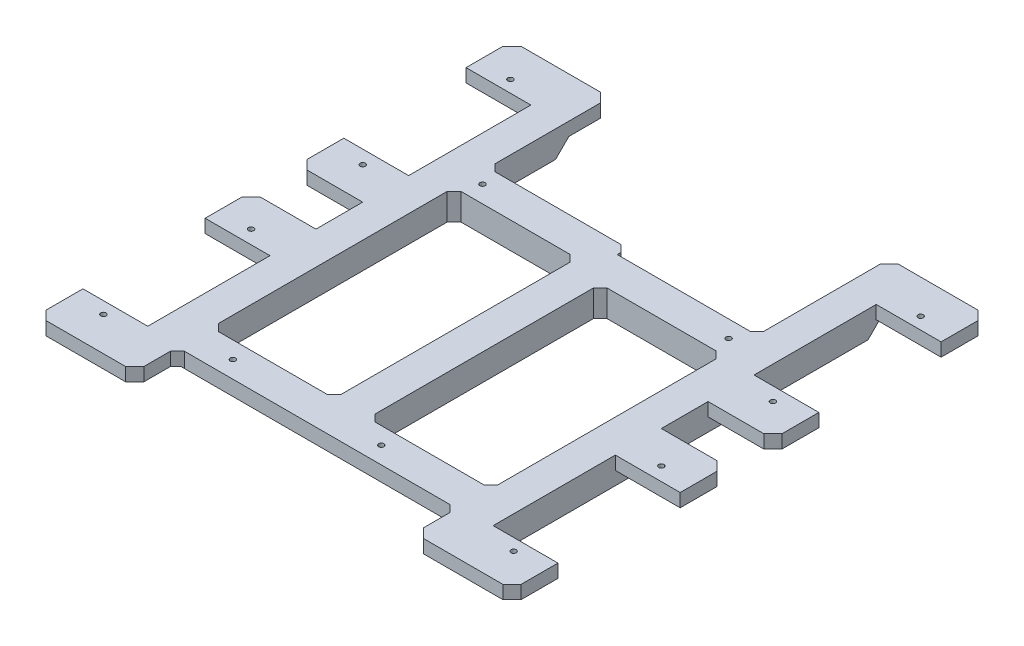
SolidWorks part; units mm, degrees
other "Markup1"
sketch "Sketch8" plane through (-44.7, 2.5, -44.7) normal (0, 1, 0) x (1, 0, 0)
sketch "Sketch10" plane through (-44.7, 2.5, -44.7) normal (0, 1, 0) x (1, 0, 0)
sketch "Sketch12" plane through (-44.7, 2.5, -44.7) normal (0, 1, 0) x (1, 0, 0)
sketch "Sketch14" plane through (-44.7, 2.5, -44.7) normal (0, 1, 0) x (1, 0, 0)
other "Markup2"
sketch "Sketch9" plane through (-44.7, 2.5, -44.7) normal (0, 1, 0) x (1, 0, 0)
sketch "Sketch11" plane through (-44.7, 2.5, -44.7) normal (0, 1, 0) x (1, 0, 0)
sketch "Sketch13" plane through (-44.7, 2.5, -44.7) normal (0, 1, 0) x (1, 0, 0)
sketch "Sketch15" plane through (-44.7, 2.5, -44.7) normal (0, 1, 0) x (1, 0, 0)
ref_plane "Front Plane" through (0, 0, 0) normal (0, 0, 1) x (1, 0, 0)
ref_plane "Top Plane" through (0, 0, 0) normal (0, 1, 0) x (1, 0, 0)
ref_plane "Right Plane" through (0, 0, 0) normal (1, 0, 0) x (0, 0, -1)
sketch "Sketch1" plane through (0, 0, 0) normal (0, 1, 0) x (1, 0, 0)
  line L0 (0, 44.7) -> (0, -44.7) construction
  line L1 (44.7, -44.7) -> (-44.7, -44.7)
  line L2 (44.7, -44.7) -> (44.7, 44.7)
  line L3 (44.7, 44.7) -> (-44.7, 44.7)
  line L4 (-44.7, -44.7) -> (-44.7, 44.7)
  line L5 (44.7, -44.7) -> (-44.7, 44.7) construction
  line L6 (44.7, 44.7) -> (-44.7, -44.7) construction
  circle A4 centre (-38.6, 38.3) radius 0.5
  circle A5 centre (-38.6, 10.5) radius 0.5
  circle A6 centre (-38.6, -10.5) radius 0.5
  circle A7 centre (-38.6, -38.3) radius 0.5
  circle A16 centre (38.6, -38.3) radius 0.5
  circle A17 centre (38.6, -10.5) radius 0.5
  circle A18 centre (38.6, 10.5) radius 0.5
  circle A19 centre (38.6, 38.3) radius 0.5
  point P0 (0, 0)
  point P6 (0, 0)
  dimension "D17" = 1
  dimension "D20" = 1
  dimension "D23" = 1
  dimension "D26" = 1
  dimension "D1" = 89.4
  dimension "D2" = 89.4
  dimension "D18" = 6.4
  dimension "D19" = 6.1
  dimension "D21" = 6.1
  dimension "D22" = 27.8
  dimension "D24" = 6.1
  dimension "D25" = 6.4
  dimension "D27" = 6.1
  dimension "D28" = 27.8
extrude "Boss-Extrude1" add sketch "Sketch1" along normal blind 2.5
sketch "Sketch5" plane through (0, 0, 0) normal (0, -1, 0) x (1, 0, 0)
  line L1 (32.5, -37) -> (-32.5, -37)
  line L2 (32.5, -37) -> (32.5, 37)
  line L3 (32.5, 37) -> (-32.5, 37)
  line L4 (-32.5, -37) -> (-32.5, 37)
  line L5 (32.5, -37) -> (-32.5, 37) construction
  line L6 (32.5, 37) -> (-32.5, -37) construction
  point P0 (0, 0)
  dimension "D1" = 65
  dimension "D2" = 74
extrude "Boss-Extrude3" add sketch "Sketch5" along normal blind 2.5
sketch "Sketch7" plane through (0, 2.5, 0) normal (0, 1, 0) x (1, 0, 0)
  line L1 (30.5, -35) -> (-30.5, -35) construction
  line L2 (30.5, -35) -> (30.5, 35) construction
  line L3 (30.5, 35) -> (-30.5, 35) construction
  line L4 (-30.5, -35) -> (-30.5, 35) construction
  line L5 (30.5, -35) -> (-30.5, 35) construction
  line L6 (30.5, 35) -> (-30.5, -35) construction
  circle A0 centre (-24.15, 18.595) radius 0.5
  circle A1 centre (24.15, 16.605) radius 0.5
  circle A2 centre (-19.07, -33.475) radius 0.5
  circle A3 centre (8.86, -33.475) radius 0.5
  point P0 (0, 0)
  dimension "D3" = 1
  dimension "D6" = 1
  dimension "D9" = 1
  dimension "D12" = 1
  dimension "D13" = 3.05
  dimension "D1" = 70
  dimension "D2" = 61
  dimension "D4" = 6.35
  dimension "D5" = 52.07
  dimension "D7" = 6.35
  dimension "D8" = 50.08
  dimension "D10" = 3.05
  dimension "D11" = 11.43
  dimension "D14" = 21.64
extrude "Cut-Extrude2" cut sketch "Sketch7" against normal blind 4
sketch "Sketch2" plane through (0, 2.5, 0) normal (0, 1, 0) x (1, 0, 0)
  line L0 (44.7, 44.7) -> (-44.7, 44.7) construction
  line L1 (-44.7, 40.6) -> (-32.5, 40.6) construction
  line L2 (-44.7, 40.6) -> (-44.7, 8.5) construction
  line L3 (-44.7, 8.5) -> (-32.5, 8.5) construction
  line L4 (-32.5, 40.6) -> (-32.5, 8.5) construction
  line L5 (-44.7, 40.6) -> (-32.5, 8.5) construction
  line L6 (-44.7, 8.5) -> (-32.5, 40.6) construction
  line L7 (-44.7, 44.7) -> (-44.7, -44.7) construction
  line L8 (0, 44.7) -> (0, -44.7) construction
  line L9 (-44.7, -44.7) -> (44.7, -44.7) construction
  line L10 (-44.7, 0) -> (44.7, 0) construction
  line L11 (44.7, -44.7) -> (44.7, 44.7) construction
  line L12 (-44.7, -8.5) -> (-32.5, -40.6) construction
  line L13 (-44.7, -40.6) -> (-32.5, -8.5) construction
  line L14 (-32.5, -40.6) -> (-32.5, -8.5) construction
  line L15 (-44.7, -8.5) -> (-32.5, -8.5) construction
  line L16 (-44.7, -40.6) -> (-44.7, -8.5) construction
  line L17 (-44.7, -40.6) -> (-32.5, -40.6) construction
  line L18 (44.7, -40.6) -> (32.5, -40.6) construction
  line L19 (44.7, -40.6) -> (44.7, -8.5) construction
  line L20 (44.7, -8.5) -> (32.5, -8.5) construction
  line L21 (32.5, -40.6) -> (32.5, -8.5) construction
  line L22 (44.7, -40.6) -> (32.5, -8.5) construction
  line L23 (44.7, -8.5) -> (32.5, -40.6) construction
  line L24 (44.7, 8.5) -> (32.5, 40.6) construction
  line L25 (44.7, 40.6) -> (32.5, 8.5) construction
  line L26 (32.5, 40.6) -> (32.5, 8.5) construction
  line L27 (44.7, 8.5) -> (32.5, 8.5) construction
  line L28 (44.7, 40.6) -> (44.7, 8.5) construction
  line L29 (44.7, 40.6) -> (32.5, 40.6) construction
  line L31 (-32.5, 13.05) -> (-44.7, 13.05)
  line L32 (-32.5, 13.05) -> (-32.5, 36.05)
  line L33 (-32.5, 36.05) -> (-44.7, 36.05)
  line L34 (-44.7, 13.05) -> (-44.7, 36.05)
  line L35 (-32.5, 13.05) -> (-44.7, 36.05) construction
  line L36 (-32.5, 36.05) -> (-44.7, 13.05) construction
  line L48 (44.7, 44.7) -> (-44.7, 44.7) construction
  line L49 (-26.3, 44.7) -> (26.3, 44.7)
  line L50 (-26.3, 44.7) -> (-26.3, 21.795)
  line L51 (-26.3, 21.795) -> (0, 21.795)
  line L52 (26.3, 44.7) -> (26.3, 24.23)
  line L53 (44.7, -44.7) -> (-44.7, -44.7) construction
  line L54 (-26.3, -44.7) -> (26.3, -44.7)
  line L55 (-26.3, -44.7) -> (-26.3, -36.675)
  line L56 (-26.3, -36.675) -> (26.3, -36.675)
  line L57 (26.3, -44.7) -> (26.3, -36.675)
  line L58 (-44.7, -44.7) -> (-44.7, 44.7) construction
  line L59 (-26.3, 15.395) -> (-3.2, 15.395)
  line L60 (-26.3, 15.395) -> (-26.3, -30.275)
  line L61 (-26.3, -30.275) -> (-3.2, -30.275)
  line L62 (-3.2, 15.395) -> (-3.2, -30.275)
  line L63 (3.2, 13.405) -> (26.3, 13.405)
  line L64 (3.2, 13.405) -> (3.2, -30.275)
  line L65 (3.2, -30.275) -> (26.3, -30.275)
  line L66 (26.3, 13.405) -> (26.3, -30.275)
  line L67 (-44.7, 4.4) -> (-32.5, 4.4)
  line L68 (-44.7, 4.4) -> (-44.7, -4.4)
  line L69 (-44.7, -4.4) -> (-32.5, -4.4)
  line L70 (-32.5, 4.4) -> (-32.5, -4.4)
  line L71 (44.7, -44.7) -> (44.7, 44.7) construction
  line L72 (44.7, 4.4) -> (32.5, 4.4)
  line L73 (44.7, 4.4) -> (44.7, -4.4)
  line L74 (44.7, -4.4) -> (32.5, -4.4)
  line L75 (32.5, 4.4) -> (32.5, -4.4)
  line L76 (32.5, 36.05) -> (44.7, 36.05)
  line L78 (26.3, 24.23) -> (26.3, 19.805)
  line L79 (26.3, 19.805) -> (0, 19.805)
  line L80 (0, 21.795) -> (0, 19.805)
  line L81 (44.7, 13.05) -> (44.7, 36.05)
  line L82 (32.5, 13.05) -> (44.7, 13.05)
  line L83 (32.5, 13.05) -> (32.5, 36.05)
  line L84 (32.5, -13.05) -> (32.5, -36.05)
  line L85 (32.5, -13.05) -> (44.7, -13.05)
  line L86 (44.7, -13.05) -> (44.7, -36.05)
  line L87 (32.5, -36.05) -> (44.7, -36.05)
  line L88 (-32.5, -36.05) -> (-44.7, -36.05)
  line L89 (-44.7, -13.05) -> (-44.7, -36.05)
  line L90 (-32.5, -13.05) -> (-44.7, -13.05)
  line L91 (-32.5, -13.05) -> (-32.5, -36.05)
  point P0 (-38.6, 24.55)
  point P5 (-38.6, 40.6)
  point P23 (-38.6, -24.55)
  point P32 (38.6, -24.55)
  point P33 (38.6, 24.55)
  point P34 (-38.6, 24.55)
  dimension "D1" = 32.1
  dimension "D2" = 12.2
  dimension "D3" = 4.1
  dimension "D4" = 23
  dimension "D5" = 3.2
  dimension "D6" = 3.2
  dimension "D7" = 3.2
  dimension "D8" = 3.2
  dimension "D9" = 6.2
  dimension "D10" = 6.2
  dimension "D11" = 6.2
  dimension "D12" = 6.2
  dimension "D13" = 6.2
  dimension "D14" = 6.2
  dimension "D15" = 3.2
  dimension "D16" = 3.2
  dimension "D17" = 3.2
  dimension "D18" = 3.2
  dimension "D19" = 3.2
  dimension "D20" = 4.1
  dimension "D21" = 4.1
  dimension "D22" = 6.2
  dimension "D23" = 4.1
  dimension "D24" = 4.1
  dimension "D25" = 6.2
extrude "Cut-Extrude1" cut sketch "Sketch2" against normal through all both and the other way through all
chamfer "Chamfer2" distance 1.3 angle 45 1 edges at (0, 0, -21.795)
chamfer "Chamfer3" distance 1.3 angle 45 12 edges at (-26.3, 0, -21.795) (26.3, 0, 36.675) (-26.3, 0, 36.675) (-26.3, 0, 30.275) (-3.2, 0, 30.275) (3.2, 0, 30.275) (26.3, 0, 30.275) (-3.2, 0, -15.395) (3.2, 0, -13.405) (26.3, 0, -13.405) (26.3, 0, -19.805) (-26.3, 0, -15.395)
chamfer "Chamfer4" distance 1.7 angle 45 12 edges at (44.7, 1.25, 4.4) (44.7, 1.25, -4.4) (-44.7, 1.25, 4.4) (-44.7, 1.25, -4.4) (44.7, 1.25, 44.7) (26.3, 1.25, 44.7) (-26.3, 1.25, 44.7) (-44.7, 1.25, 44.7) (44.7, 1.25, -44.7) (26.3, 1.25, -44.7) (-26.3, 1.25, -44.7) (-44.7, 1.25, -44.7)
chamfer "Chamfer5" distance 2.5 angle 45 3 edges at (28.9125, -2.5, 37) (29.4, -2.5, -37) (-29.4, -2.5, -37)
